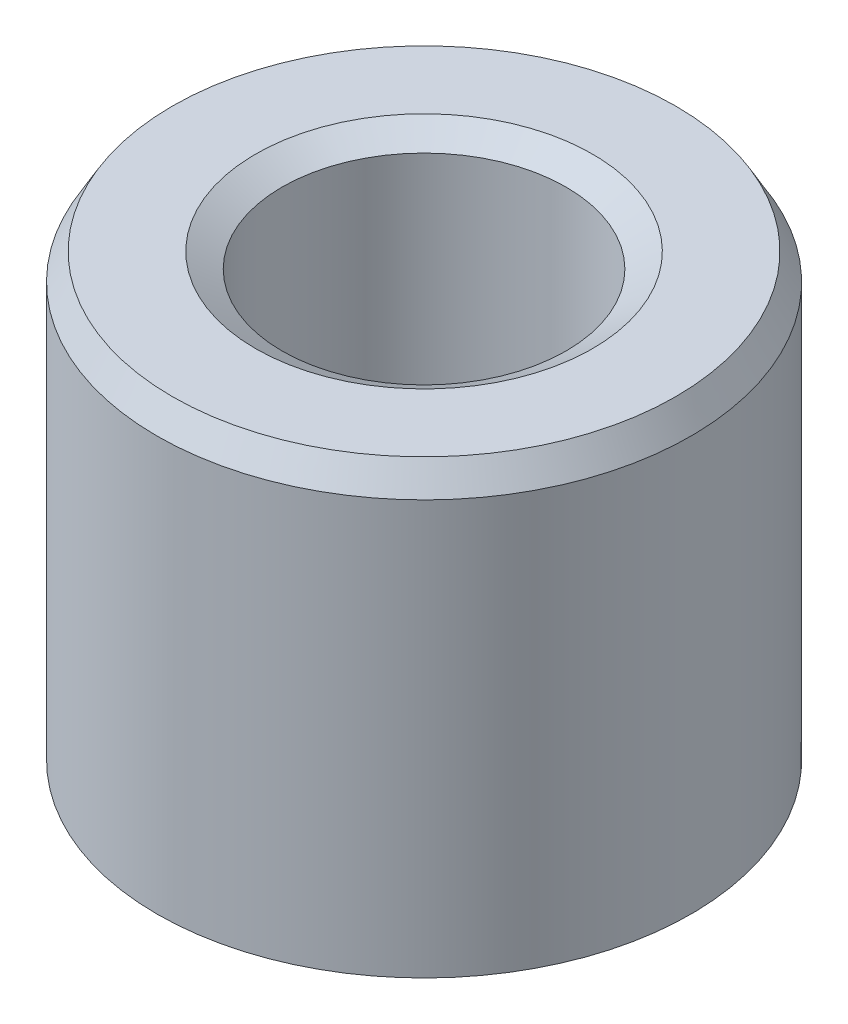
SolidWorks part; units mm, degrees
ref_plane "Front Plane" through (0, 0, 0) normal (0, 0, 1) x (1, 0, 0)
ref_plane "Top Plane" through (0, 0, 0) normal (0, 1, 0) x (1, 0, 0)
ref_plane "Right Plane" through (0, 0, 0) normal (1, 0, 0) x (0, 0, -1)
sketch "Sketch1" plane through (0, 0, 0) normal (0, 1, 0) x (1, 0, 0)
  circle A0 centre (0, 0) radius 5
  dimension "SLEEVE_OD" = 10
extrude "Boss-Extrude1" add sketch "Sketch1" along normal blind 8.5366
sketch "Sketch2" plane through (0, 0, 0) normal (0, 1, 0) x (1, 0, 0)
  circle A0 centre (0, 0) radius 2.6598
  dimension "BORE_D" = 5.3197
extrude "Cut-Extrude1" cut sketch "Sketch2" along normal through all
chamfer "Chamfer1" distance 0.496 angle 30 4 edges at (0, 8.5366, 2.6598) (0, 0, 2.6598) (0, 0, 5) (0, 8.5366, 5) first distance on face at (0, 8.5366, 2.6598) first distance on face at (0, 0, 2.6598) first distance on face at (0, 8.5366, 5)
